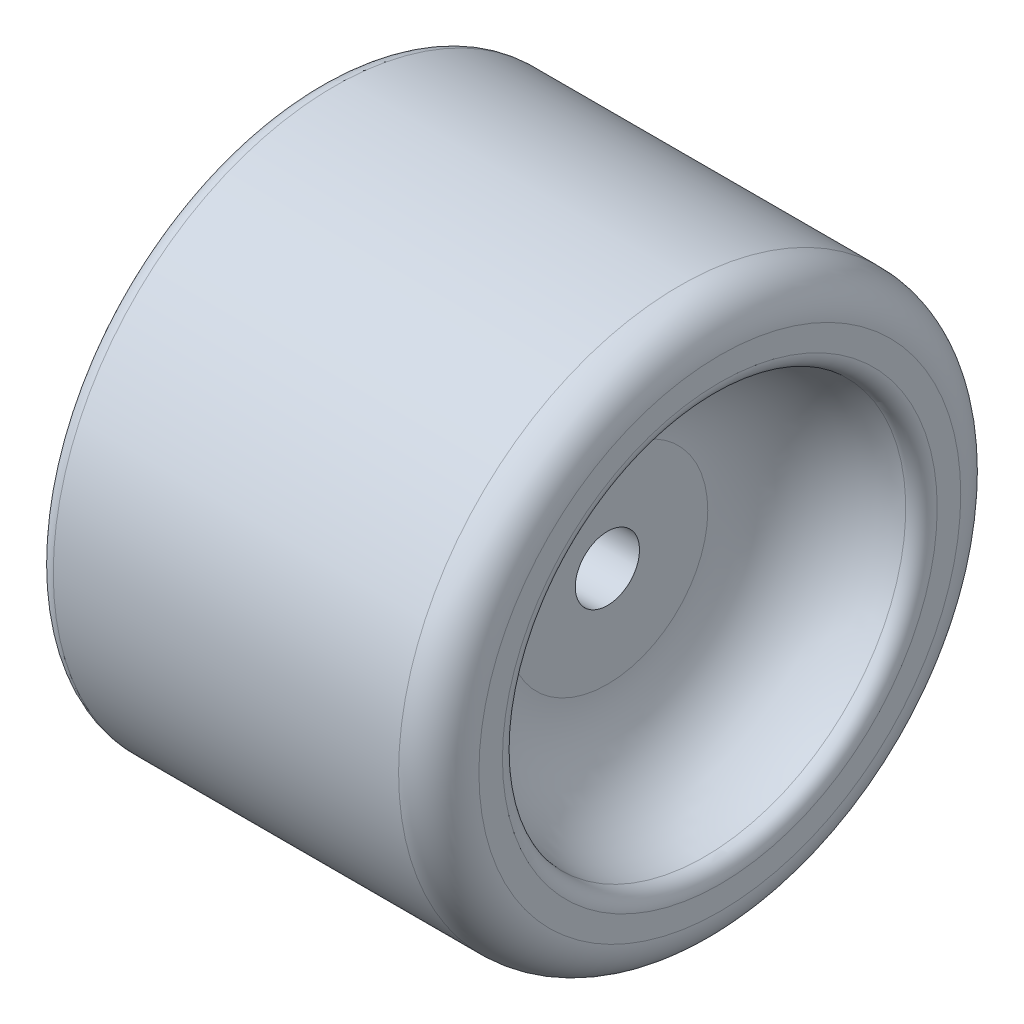
SolidWorks part; units mm, degrees
ref_plane "Front Plane" through (0, 0, 0) normal (0, 0, 1) x (1, 0, 0)
ref_plane "Top Plane" through (0, 0, 0) normal (0, 1, 0) x (1, 0, 0)
ref_plane "Right Plane" through (0, 0, 0) normal (1, 0, 0) x (0, 0, -1)
ref_plane "Plane1" through (0, 0, 0) normal (0, 0, -1) x (-1, 0, 0)
sketch "Sketch1" plane through (0, 0, 0) normal (0, 0, -1) x (-1, 0, 0)
  line L0 (0, 4) -> (22, 4)
  line L1 (22, 4) -> (22, 12.5)
  line L2 (22, 12.5) -> (24.5624, 12.5)
  line L3 (36, 29.2029) -> (36, 33)
  line L4 (34, 35) -> (-9, 35)
  line L5 (-14, 30) -> (-14, 27.0688)
  line L6 (0, 12.5) -> (0, 4)
  line L7 (-14.0021, 0) -> (36.0023, 0) construction
  arc A0 (24.5624, 12.5) -> (25.0573, 12.9284) centre (24.5624, 13) ccw
  arc A1 (25.0573, 12.9284) -> (34.9865, 27.4631) centre (44.8512, 10.0652) cw
  arc A2 (34.9865, 27.4631) -> (36, 29.2029) centre (34, 29.2029) ccw
  arc A3 (36, 33) -> (34, 35) centre (34, 33) ccw
  arc A4 (-9, 35) -> (-14, 30) centre (-9, 30) ccw
  arc A5 (-14, 27.0688) -> (-12.0796, 25.0704) centre (-12, 27.0688) ccw
  arc A6 (-12.0796, 25.0704) -> (0, 12.5) centre (-12.5804, 12.5) cw
revolve "Revolve1" add sketch "Sketch1" angle 360 about L7 reverse direction yes
